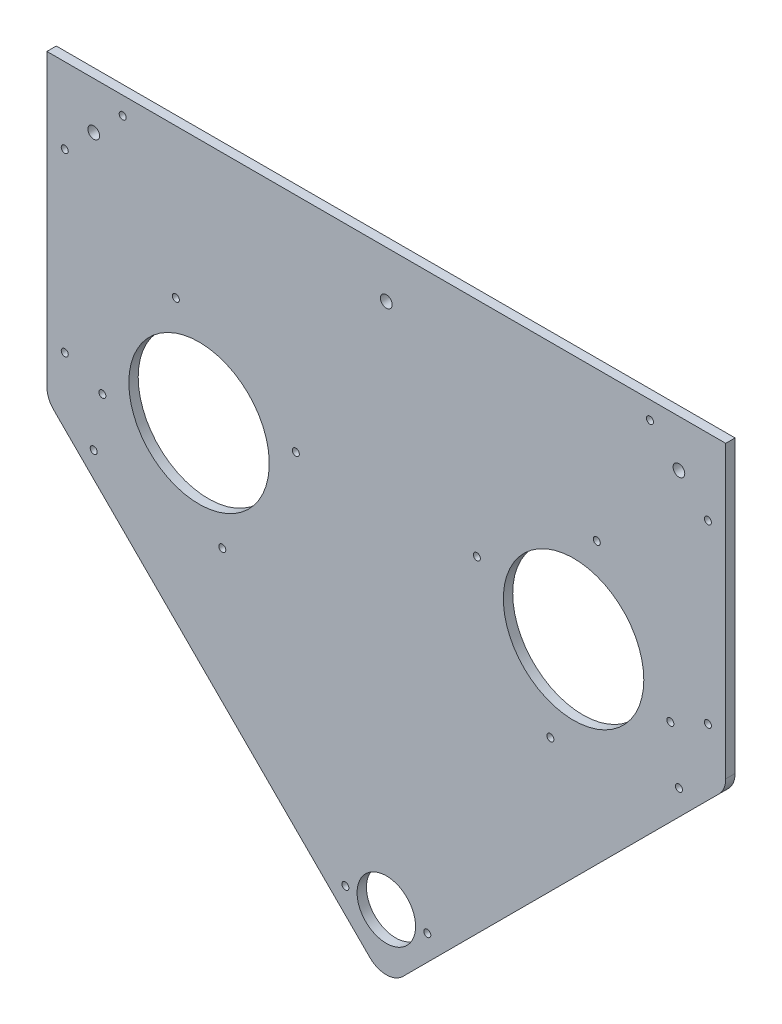
SolidWorks part; units mm, degrees
ref_plane "Front Plane" through (0, 0, 0) normal (0, 0, 1) x (1, 0, 0)
ref_plane "Top Plane" through (0, 0, 0) normal (0, 1, 0) x (1, 0, 0)
ref_plane "Right Plane" through (0, 0, 0) normal (1, 0, 0) x (0, 0, -1)
sketch "Sketch1" plane through (0, 0, 0) normal (0, 0, 1) x (1, 0, 0)
  line L0 (-125, 100) -> (125, 100) construction
  line L1 (-125, 0) -> (125, 0) construction
  line L2 (-137.3744, 87.6256) -> (-125, 100) construction
  line L3 (0, -125) -> (-125, 0) construction
  line L4 (0, -125) -> (-17.5, -125) construction
  line L5 (-125, -17.5) -> (-125, 0) construction
  line L6 (0, -125) -> (0, 100) construction
  line L7 (-145, 120) -> (145, 120)
  line L8 (145, 120) -> (145, -8.2843)
  line L9 (145, -8.2843) -> (0, -153.2843)
  line L10 (0, -153.2843) -> (-145, -8.2843)
  line L11 (-145, -8.2843) -> (-145, 120)
  circle A0 centre (-125, 100) radius 12.5 construction
  circle A1 centre (125, 100) radius 12.5 construction
  circle A4 centre (0, -125) radius 12.5
  circle A5 centre (-137.3744, 87.6256) radius 1.5
  circle A6 centre (-112.6256, 112.3744) radius 1.5
  circle A7 centre (-137.3744, 12.3744) radius 1.5
  circle A8 centre (-125, -17.5) radius 1.5
  circle A9 centre (-17.5, -125) radius 1.5
  circle A10 centre (-125, 0) radius 12.5 construction
  circle A11 centre (125, 0) radius 12.5 construction
  circle A12 centre (-125, 0) radius 17.5 construction
  circle A13 centre (-125, 100) radius 17.5 construction
  circle A14 centre (0, -125) radius 17.5 construction
  circle A15 centre (17.5, -125) radius 1.5
  circle A16 centre (125, -17.5) radius 1.5
  circle A17 centre (137.3744, 12.3744) radius 1.5
  circle A18 centre (137.3744, 87.6256) radius 1.5
  circle A19 centre (112.6256, 112.3744) radius 1.5
  circle A20 centre (0, 100) radius 2.5
  circle A21 centre (-125, 100) radius 2.5
  circle A22 centre (125, 100) radius 2.5
  point P12 (0, 100)
  point P45 (0, 120)
  dimension "D1" = 25
  dimension "D5" = 3
  dimension "D2" = 5
  dimension "D4" = 100
  dimension "D6" = 5
  dimension "D7" = 135
  dimension "D8" = 45
  dimension "D9" = 250
  dimension "D10" = 45
  dimension "D11" = 20
  dimension "D12" = 20
  dimension "D13" = 20
  dimension "D14" = 20
  dimension "D15" = 20
  dimension "D3" = 125
  dimension "D16" = 75.2513
  dimension "D17" = 152.028
  dimension "D18" = 225.2513
extrude "Boss-Extrude1" add sketch "Sketch1" along normal blind 4
fillet "Fillet1" radius 10 3 edges at (-145, -8.2843, 2) (145, -8.2843, 2) (0, -153.2843, 2)
sketch "Sketch2" plane through (0, 0, 4) normal (0, 0, 1) x (1, 0, 0)
  line L0 (121.326, 5.0796) -> (38.674, 24.9204) construction
  line L1 (70.0796, -26.326) -> (89.9204, 56.326) construction
  line L2 (0, 0) -> (0, 100) construction
  line L3 (145, 120) -> (-145, 120) construction
  line L4 (-145, 120) -> (-145, -4.1421) construction
  circle A0 centre (80, 15) radius 42.5 construction
  circle A1 centre (38.674, 24.9204) radius 1.5
  circle A2 centre (89.9204, 56.326) radius 1.5
  circle A3 centre (121.326, 5.0796) radius 1.5
  circle A4 centre (70.0796, -26.326) radius 1.5
  circle A5 centre (80, 15) radius 30
  circle A6 centre (-38.674, 24.9204) radius 1.5
  circle A7 centre (-89.9204, 56.326) radius 1.5
  circle A8 centre (-70.0796, -26.326) radius 1.5
  circle A9 centre (-121.326, 5.0796) radius 1.5
  circle A10 centre (-80, 15) radius 42.5 construction
  circle A11 centre (-80, 15) radius 30
  circle A12 centre (-80, 15) radius 47.5 construction
  circle A13 centre (-137.3744, 12.3744) radius 3 construction
  circle A14 centre (-125, -17.5) radius 3 construction
  point P6 (80, 15)
  point P27 (-80, 15)
  dimension "D1" = 85
  dimension "D2" = 3
  dimension "D3" = 60
  dimension "D4" = 95
  dimension "D5" = 6
  dimension "D6" = 105
  dimension "D7" = 65
extrude "Cut-Extrude1" cut sketch "Sketch2" against normal blind 10
equation "\"D1@Sketch1\" = \"cf_tube_outer_diameter\""
equation "\"D9@Sketch1\"= \"mid_plate_horizontal_spacing\""
equation "\"mid_plate_mid_to_top\" = 100mm"
equation "\"mid_plate_mid_to_bottom\" = 125mm"
equation "\"mid_plate_horizontal_spacing\" = 250mm"
equation "\"cf_tube_outer_diameter\" = 25mm"
equation "\"D4@Sketch1\"=\"mid_plate_mid_to_top\""
equation "\"D3@Sketch1\"=\"mid_plate_mid_to_bottom\""
equation "\"cf_tube_inner_diameter\" = 21mm"
equation "\"mid_tube_length\" = 500mm"
equation "\"cf_plate_thickness\" = 4mm"
equation "\"D1@Boss-Extrude1\"=\"cf_plate_thickness\""
